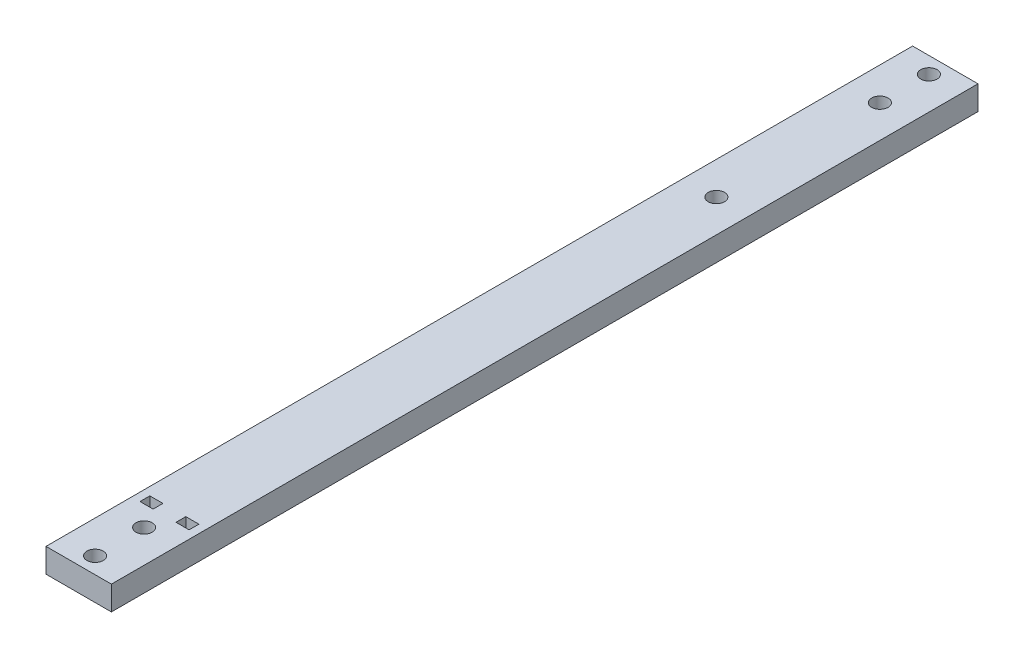
SolidWorks part; units mm, degrees
ref_plane "前视基准面" through (0, 0, 0) normal (0, 0, 1) x (1, 0, 0)
ref_plane "上视基准面" through (0, 0, 0) normal (0, 1, 0) x (1, 0, 0)
ref_plane "右视基准面" through (0, 0, 0) normal (1, 0, 0) x (0, 0, -1)
other "Configuration Table"
sketch "草图1" plane through (0, 0, 0) normal (0, 1, 0) x (1, 0, 0)
  line L1 (0, 0) -> (8, 0)
  line L2 (0, 0) -> (0, -106)
  line L3 (0, -106) -> (8, -106)
  line L4 (8, 0) -> (8, -106)
  dimension "D1" = 106
  dimension "D2" = 8
extrude "凸台-拉伸1" add sketch "草图1" along normal blind 2.95
sketch "草图2" plane through (0, 2.95, 0) normal (0, 1, 0) x (1, 0, 0)
  line L0 (0, -2) -> (8, -2)
  line L1 (0, 0) -> (0, -106) construction
  line L2 (8, -106) -> (8, 0) construction
  line L3 (8, 0) -> (0, 0) construction
  line L4 (0, -106) -> (8, -106) construction
  circle A0 centre (4, -8) radius 0.7
  circle A1 centre (4, -8) radius 1
  circle A2 centre (4, -2) radius 0.7
  circle A3 centre (4, -2) radius 1
  circle A4 centre (4, -104) radius 0.7
  circle A5 centre (4, -104) radius 1
  circle A6 centre (4, -98) radius 0.7
  circle A7 centre (4, -98) radius 1
  circle A8 centre (4, -28) radius 1
  circle A9 centre (4, -28) radius 0.7
  dimension "D1" = 2
  dimension "D2" = 1.4
  dimension "D3" = 2
  dimension "D4" = 1.4
  dimension "D7" = 2
  dimension "D8" = 1.4
  dimension "D9" = 2
  dimension "D10" = 1.4
  dimension "D5" = 2
  dimension "D6" = 6
  dimension "D11" = 2
  dimension "D12" = 6
  dimension "D13" = 20
extrude "切除-拉伸1" cut sketch "草图2" against normal through all contours A2 | A0 | A6 | A4 | A9
extrude "切除-拉伸2" cut sketch "草图2<3>" against normal blind 1.5 contours A1 | A3 | A5 | A7 | A8
sketch "草图2<3>" plane through (0, 2.95, 0) normal (0, 1, 0) x (1, 0, 0) same geometry as "草图2"
sketch "草图3" plane through (0, 2.95, 0) normal (0, 1, 0) x (1, 0, 0)
  line L0 (0, 0) -> (0, -106) construction
  line L1 (1, -94.3) -> (2.6, -94.3)
  line L2 (1, -94.3) -> (1, -95.5)
  line L3 (1, -95.5) -> (2.6, -95.5)
  line L4 (2.6, -94.3) -> (2.6, -95.5)
  line L5 (5.4, -94.3) -> (7, -94.3)
  line L6 (5.4, -94.3) -> (5.4, -95.5)
  line L7 (5.4, -95.5) -> (7, -95.5)
  line L8 (7, -94.3) -> (7, -95.5)
  line L9 (8, -106) -> (8, 0) construction
  line L10 (0, -106) -> (8, -106) construction
  dimension "D1" = 1
  dimension "D2" = 1
  dimension "D3" = 1.6
  dimension "D4" = 1.2
  dimension "D5" = 10.5
extrude "切除-拉伸3" cut sketch "草图3" against normal through all contours L4 L1 L2 L3 | L8 L5 L6 L7 region at (1.8, 2.95, 94.9) region at (6.2, 2.95, 94.9)
